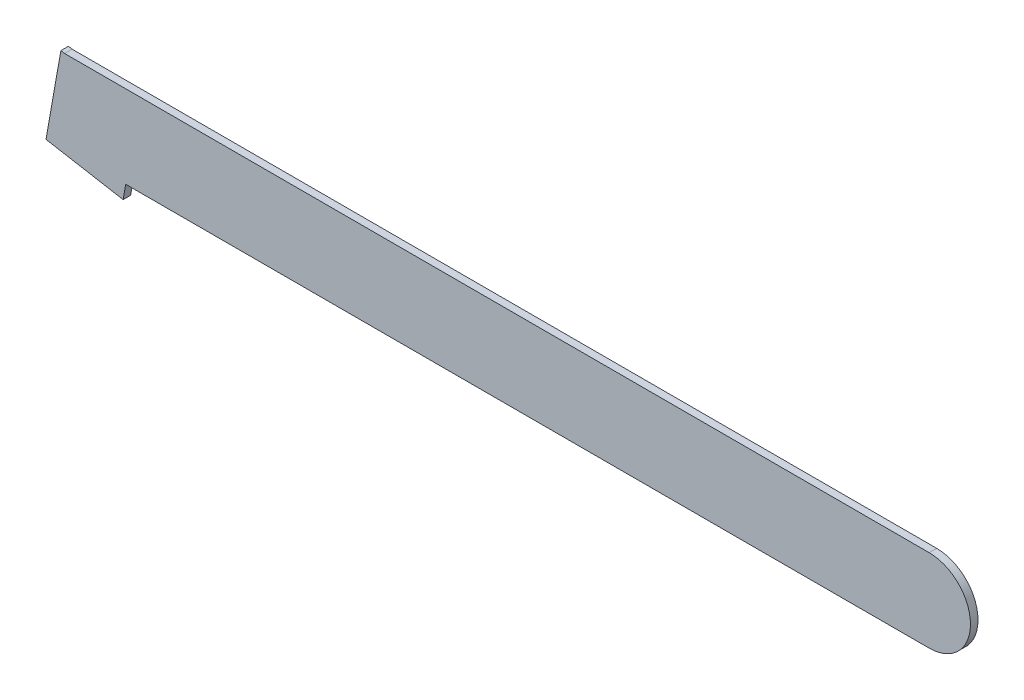
SolidWorks part; units mm, degrees
ref_plane "Front" through (0, 0, 0) normal (0, 0, 1) x (1, 0, 0)
ref_plane "Top" through (0, 0, 0) normal (0, 1, 0) x (1, 0, 0)
ref_plane "Right" through (0, 0, 0) normal (1, 0, 0) x (0, 0, -1)
sketch "Sketch1" plane through (0, 0, 0) normal (0, 0, 1) x (1, 0, 0)
  line L0 (-2300, 110) -> (-2309.8481, 111.7365)
  line L1 (0, 110) -> (-2300, 110)
  line L3 (0, -110) -> (-2137.4035, -110)
  line L5 (-2309.8481, 111.7365) -> (-2344.2096, -83.1373)
  line L10 (-2344.2096, -83.1373) -> (-2349.419, -112.6815)
  line L11 (-2137.4035, -110) -> (-2144.2552, -148.8574)
  line L12 (-2349.419, -112.6815) -> (-2144.2552, -148.8574)
  arc A2 (0, 110) -> (0, -110) centre (0, 0) cw
  point P0 (0, 0)
  dimension "D2" = 110
  dimension "D1" = 2300
  dimension "D3" = 110
  dimension "D4" = 30
  dimension "D5" = 10
  dimension "D6" = 2344.2096
  dimension "D7" = 197.88
  dimension "D8" = 39.4569
extrude "Boss-Extrude1" add sketch "Sketch1" along normal mid plane 20
